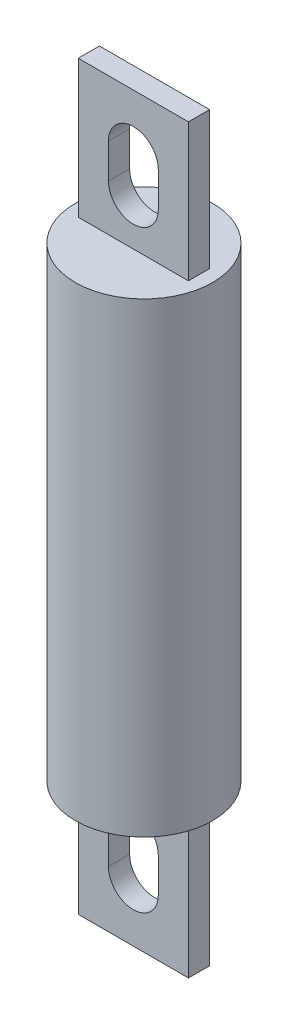
SolidWorks part; units mm, degrees
ref_plane "X-Y Datum" through (0, 0, 0) normal (0, 0, 1) x (1, 0, 0)
ref_plane "X-Z Datum" through (0, 0, 0) normal (0, 1, 0) x (1, 0, 0)
ref_plane "Y-Z Datum" through (0, 0, 0) normal (1, 0, 0) x (0, 0, -1)
sketch "Sketch1" plane through (0, 0, 0) normal (0, 1, 0) x (1, 0, 0)
  circle A0 centre (0, 0) radius 10.287
  dimension "D1" = 20.574
extrude "Boss-Extrude1" add sketch "Sketch1" along normal blind 69.85
sketch "Sketch2" plane through (0, 69.85, 0) normal (0, 1, 0) x (1, 0, 0)
  line L1 (-8.255, -1.5875) -> (8.255, -1.5875)
  line L2 (-8.255, -1.5875) -> (-8.255, 1.5875)
  line L3 (-8.255, 1.5875) -> (8.255, 1.5875)
  line L4 (8.255, -1.5875) -> (8.255, 1.5875)
  line L5 (-8.255, -1.5875) -> (8.255, 1.5875) construction
  line L6 (-8.255, 1.5875) -> (8.255, -1.5875) construction
  point P0 (0, 0)
  dimension "D1" = 3.175
extrude "Boss-Extrude2" add sketch "Sketch2" along normal blind 20.6375
ref_plane "Plane1" through (0, 34.925, 0) normal (0, 1, 0) x (1, 0, 0)
sketch "Sketch3" plane through (0, 0, 1.5875) normal (0, 0, 1) x (1, 0, 0)
  line L1 (11.3157, 34.925) -> (-11.3157, 34.925) construction
  line L2 (0, 34.925) -> (0, 82.0166) construction
  line L3 (0, 82.0166) -> (0, 76.8096) construction
  line L4 (3.7338, 82.0166) -> (3.7338, 76.8096)
  line L5 (-3.7338, 82.0166) -> (-3.7338, 76.8096)
  arc A0 (3.7338, 82.0166) -> (-3.7338, 82.0166) centre (0, 82.0166) ccw
  arc A1 (-3.7338, 76.8096) -> (3.7338, 76.8096) centre (0, 76.8096) ccw
  point P5 (0, 79.4131)
  dimension "D1" = 47.0916
  dimension "D2" = 5.207
extrude "Cut-Extrude1" cut sketch "Sketch3" against normal through all
mirror "Mirror2" about plane through (0, 34.925, 0) normal (0, 1, 0) of "Cut-Extrude1", "Boss-Extrude2"
